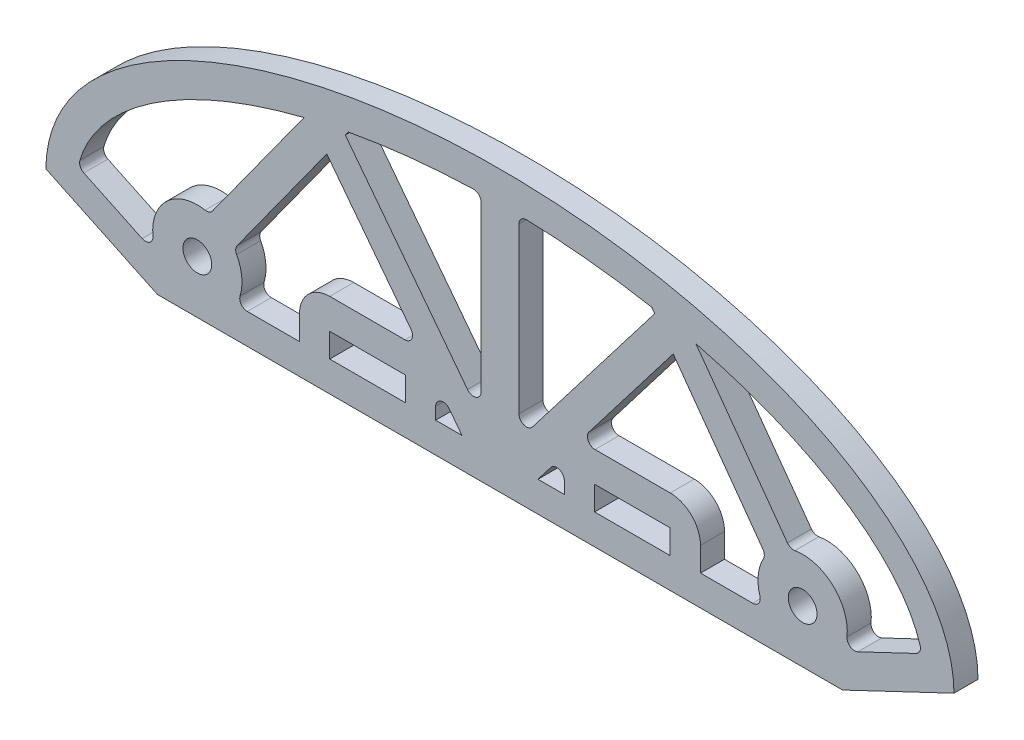
SolidWorks part; units mm, degrees
material "Mahogany"
ref_plane "Front Plane" through (0, 0, 0) normal (0, 0, 1) x (1, 0, 0)
ref_plane "Top Plane" through (0, 0, 0) normal (0, 1, 0) x (1, 0, 0)
ref_plane "Right Plane" through (0, 0, 0) normal (1, 0, 0) x (0, 0, -1)
sketch "Sketch3" plane through (0, 0, 0) normal (0, 0, 1) x (1, 0, 0)
  line L0 (85.2659, 27.2) -> (74.7341, 27.2) construction
  line L1 (74.7341, 27.2) -> (74.7341, 15.2) construction
  line L2 (74.7341, 15.2) -> (85.2659, 15.2) construction
  line L3 (85.2659, 15.2) -> (85.2659, 27.2) construction
  line L4 (5.2659, 27.2) -> (-5.2659, 27.2) construction
  line L5 (-5.2659, 27.2) -> (-5.2659, 15.2) construction
  line L6 (-5.2659, 15.2) -> (5.2659, 15.2) construction
  line L7 (5.2659, 15.2) -> (5.2659, 27.2) construction
  line L8 (85.2659, 27.2) -> (74.7341, 27.2) construction
  line L9 (74.7341, 27.2) -> (74.7341, 15.2) construction
  line L10 (74.7341, 15.2) -> (85.2659, 15.2) construction
  line L11 (85.2659, 15.2) -> (85.2659, 27.2) construction
  line L12 (5.2659, 27.2) -> (-5.2659, 27.2) construction
  line L13 (-5.2659, 27.2) -> (-5.2659, 15.2) construction
  line L14 (-5.2659, 15.2) -> (5.2659, 15.2) construction
  line L15 (5.2659, 15.2) -> (5.2659, 27.2) construction
  line L16 (0, 22.2) -> (80, 22.2) construction
  line L17 (-20, 22.2) -> (0, 22.2) construction
  line L18 (80, 22.2) -> (100, 22.2) construction
  line L19 (-20, 22.2) -> (-20, 52.2) construction
  line L20 (-20, 52.2) -> (40, 52.2) construction
  line L21 (-20, 22.2) -> (-5.2659, 15.2)
  line L22 (-5.2659, 15.2) -> (85.2659, 15.2)
  line L23 (85.2659, 15.2) -> (100, 22.2)
  line L24 (40, 52.2) -> (40, 15.2) construction
  line L25 (52.5, 22.375) -> (52.5, 19.2)
  line L26 (17.5, 22.375) -> (27.5, 22.375)
  line L27 (17.5, 22.375) -> (17.5, 19.2)
  line L28 (17.5, 19.2) -> (27.5, 19.2)
  line L29 (27.5, 22.375) -> (27.5, 19.2)
  line L30 (62.5, 19.2) -> (52.5, 19.2)
  line L31 (62.5, 22.375) -> (62.5, 19.2)
  line L32 (62.5, 22.375) -> (52.5, 22.375)
  circle A0 centre (80, 22.2) radius 1.9 construction
  circle A1 centre (0, 22.2) radius 1.9 construction
  circle A2 centre (80, 22.2) radius 1.9
  circle A3 centre (0, 22.2) radius 1.9
  ellipse E0 centre (40, 22.2) end of major axis (100, 22.2) minor radius 30 (100, 22.2) -> (-20, 22.2) ccw
  dimension "D1" = 30
  dimension "D2" = 60
  dimension "D3" = 10
  dimension "D4" = 3.175
  dimension "D5" = 4
  dimension "D6" = 25
extrude "Boss-Extrude1" add sketch "Sketch3" along normal blind 3.175
sketch "Sketch4" plane through (0, 0, 3.175) normal (0, 0, 1) x (1, 0, 0)
  line L0 (-15.7375, 24.6034) -> (-5.3232, 19.6557)
  line L1 (5.0804, 19.2) -> (74.9196, 19.2)
  line L2 (85.3232, 19.6557) -> (95.7375, 24.6034)
  line L3 (85.2659, 15.2) -> (100, 22.2)
  line L4 (52.5, 22.375) -> (52.5, 19.2)
  line L5 (62.5, 22.375) -> (52.5, 22.375)
  line L6 (62.5, 19.2) -> (62.5, 22.375)
  line L7 (52.5, 19.2) -> (62.5, 19.2)
  line L8 (52.5, 22.375) -> (52.5, 19.2) construction
  line L9 (62.5, 22.375) -> (52.5, 22.375) construction
  line L10 (62.5, 19.2) -> (62.5, 22.375) construction
  line L11 (52.5, 19.2) -> (62.5, 19.2) construction
  line L12 (17.5, 19.2) -> (27.5, 19.2)
  line L13 (17.5, 22.375) -> (17.5, 19.2)
  line L14 (27.5, 22.375) -> (17.5, 22.375)
  line L15 (27.5, 19.2) -> (27.5, 22.375)
  line L16 (17.5, 19.2) -> (27.5, 19.2) construction
  line L17 (17.5, 22.375) -> (17.5, 19.2) construction
  line L18 (27.5, 22.375) -> (17.5, 22.375) construction
  line L19 (27.5, 19.2) -> (27.5, 22.375) construction
  line L20 (-20, 22.2) -> (-5.2659, 15.2)
  line L21 (-5.2659, 15.2) -> (85.2659, 15.2)
  line L22 (85.2659, 15.2) -> (100, 22.2) construction
  line L23 (-20, 22.2) -> (-5.2659, 15.2) construction
  line L24 (-5.2659, 15.2) -> (85.2659, 15.2) construction
  line L25 (17.5, 26.375) -> (27.5, 26.375)
  line L26 (13.5, 22.375) -> (13.5, 19.2)
  line L27 (31.5, 22.375) -> (31.5, 19.2)
  line L28 (40, 15.2) -> (40, 52.2) construction
  line L29 (48.5, 22.375) -> (48.5, 19.2)
  line L30 (62.5, 26.375) -> (52.5, 26.375)
  line L31 (66.5, 22.375) -> (66.5, 19.2)
  line L32 (-4.364, 19.2) -> (84.364, 19.2) construction
  line L33 (-15.7375, 24.6034) -> (-4.364, 19.2) construction
  line L34 (84.364, 19.2) -> (95.7375, 24.6034) construction
  line L35 (37.5, 48.2) -> (42.5, 48.2)
  line L36 (37.5, 48.2) -> (37.5, 19.2)
  line L37 (37.5, 19.2) -> (42.5, 19.2)
  line L38 (42.5, 48.2) -> (42.5, 19.2)
  line L39 (17.0606, 45.8325) -> (37.5, 19.2) construction
  line L40 (14.9152, 45.3431) -> (34.9789, 19.2)
  line L41 (37.5, 22.485) -> (19.2406, 46.277)
  line L42 (24.947, 32.2715) -> (28.1202, 34.7068) construction
  line L43 (0, 22.2) -> (17.0606, 45.8325) construction
  line L44 (14.0952, 45.1417) -> (1.6274, 27.8711)
  line L45 (4.8705, 25.5298) -> (19.5537, 45.8691)
  line L46 (7.8613, 36.5064) -> (11.1045, 34.1651) construction
  line L47 (42.5, 19.2) -> (62.9394, 45.8325) construction
  line L48 (62.9394, 45.8325) -> (80, 22.2) construction
  line L49 (60.7594, 46.277) -> (42.5, 22.485)
  line L50 (45.0211, 19.2) -> (65.0848, 45.3431)
  line L51 (75.1295, 25.5298) -> (60.0562, 46.4094)
  line L52 (78.3726, 27.8711) -> (65.9048, 45.1417)
  line L53 (51.6297, 34.381) -> (54.8029, 31.9457) construction
  line L54 (72.1387, 36.5064) -> (68.8955, 34.1651) construction
  line L55 (19.5537, 45.8691) -> (19.9438, 46.4094)
  arc A0 (85.3232, 19.6557) -> (74.9196, 19.2) centre (80, 22.2) ccw
  circle A1 centre (80, 22.2) radius 1.9
  circle A2 centre (80, 22.2) radius 1.9 construction
  circle A3 centre (0, 22.2) radius 1.9
  circle A4 centre (0, 22.2) radius 1.9 construction
  arc A5 (5.0804, 19.2) -> (-5.3232, 19.6557) centre (0, 22.2) ccw
  circle A7 centre (0, 22.2) radius 5.9 construction
  circle A8 centre (80, 22.2) radius 5.9 construction
  arc A10 (17.5, 26.375) -> (13.5, 22.375) centre (17.5, 22.375) ccw
  arc A11 (31.5, 22.375) -> (27.5, 26.375) centre (27.5, 22.375) ccw
  arc A12 (48.5, 22.375) -> (52.5, 26.375) centre (52.5, 22.375) cw
  arc A13 (62.5, 26.375) -> (66.5, 22.375) centre (62.5, 22.375) cw
  arc A14 (28.2377, 27.9838) -> (27.4444, 26.375) centre (27.4444, 27.375) cw
  arc A15 (33.2933, 21.3963) -> (31.5, 20.7875) centre (32.5, 20.7875) ccw
  arc A16 (48.5, 20.7875) -> (46.7067, 21.3963) centre (47.5, 20.7875) ccw
  arc A17 (52.5556, 26.375) -> (51.7623, 27.9838) centre (52.5556, 27.375) cw
  ellipse E1 centre (40, 22.2) end of major axis (100, 22.2) minor radius 30 (100, 22.2) -> (-20, 22.2) ccw
  ellipse E2 centre (40, 22.2) end of major axis (100, 22.2) minor radius 30 (100, 22.2) -> (-20, 22.2) ccw construction
  spline S0 degree 1 poles (95.7375, 24.6034) (-15.7375, 24.6034) knots 0 0 1 1 construction
  spline S1 degree 3 poles (95.7375, 24.6034) (95.6622, 24.948) (95.4837, 25.6219) (94.9892, 27.0049) (94.1127, 28.758) (92.6161, 30.899) (90.0114, 33.7557) (85.6121, 37.2373) (78.6564, 40.9913) (71.8583, 43.5232) (67.3393, 44.7824) (65.7688, 45.1759) (65.4958, 45.2432) (65.2221, 45.3101) (64.7849, 45.4153) (64.1815, 45.5566) (63.356, 45.7431) (62.5185, 45.9239) (61.6693, 46.0987) (61.0635, 46.2186) (60.6425, 46.2994) (60.4083, 46.3438) (60.1738, 46.3877) (57.6339, 46.8566) (52.6559, 47.584) (44.2604, 48.2378) (35.7396, 48.2378) (27.3441, 47.584) (22.3661, 46.8566) (19.8262, 46.3877) (19.5917, 46.3438) (19.3575, 46.2994) (18.9365, 46.2186) (18.3307, 46.0987) (17.4815, 45.9239) (16.644, 45.7431) (15.8185, 45.5566) (15.2151, 45.4153) (14.7779, 45.3101) (14.5042, 45.2432) (14.2312, 45.1759) (12.6607, 44.7824) (8.1417, 43.5232) (1.3436, 40.9913) (-5.6121, 37.2373) (-10.0114, 33.7557) (-12.6161, 30.899) (-14.1127, 28.758) (-14.9892, 27.0049) (-15.4837, 25.6219) (-15.6622, 24.948) (-15.7375, 24.6034) knots 3.250373 3.250373 3.250373 3.250373 3.296061 3.341749 3.433125 3.524501 3.615877 3.798629 3.981381 4.164133 4.243947 4.251896 4.25587 4.259844 4.267792 4.281193 4.294593 4.31502 4.328713 4.342405 4.348917 4.352174 4.35543 4.361942 4.492953 4.623963 4.800815 4.931825 5.062836 5.069348 5.072604 5.075861 5.082373 5.096065 5.109758 5.130185 5.143585 5.156986 5.164934 5.168908 5.172882 5.180831 5.260645 5.443397 5.626149 5.808901 5.900277 5.991653 6.083029 6.128717 6.174405 6.174405 6.174405 6.174405
  point P42 (85.9, 22.2)
  point P43 (5.9, 22.2)
  point P53 (40, 19.2)
  point P54 (40, 48.2)
  point P68 (26.5336, 33.4892)
  point P75 (9.4829, 35.3358)
  point P79 (53.2163, 33.1633)
  point P82 (70.5171, 35.3358)
  point P104 (0, 0)
  point P105 (0, 0)
  point P106 (47.0571, 21.8529)
  dimension "D7" = 4
  dimension "D10" = 4
  dimension "D14" = 1
  dimension "D9" = 5
  dimension "D11" = 4
  dimension "D12" = 4
  dimension "D13" = 4
  dimension "D1" = 0
  dimension "D2" = 0
  dimension "D3" = 0
  dimension "D4" = 0
  dimension "D5" = 0
  dimension "D6" = 4
  dimension "D8" = 4
extrude "Cut-Extrude2" cut sketch "Sketch4" against normal up to surface (3.175 mm away) contours L44 S1 L0 A5 | A14 L40 L45 A5 L1 L26 A10 L25 | L36 S1 L55 L41 | L40 A15 L27 L1 | L51 S1 L38 L49 | L29 A16 L50 L1 | A17 L30 A13 L31 L1 A0 L51 L50 | L2 S1 L52 A0 region at (-2.3557, 32.6493, 3.175) region at (15.5054, 29.6634, 3.175) region at (31.3607, 39.1382, 3.175) region at (32.846, 20.2705, 3.175) region at (48.6393, 39.1382, 3.175) region at (47.154, 20.2705, 3.175) region at (64.4946, 29.6634, 3.175) region at (82.3557, 32.6493, 3.175) up to face at (57.5, 20.7875, 0)
fillet "Fillet1" radius 1 14 edges at (95.7375, 24.6034, 1.5875) (-15.7375, 24.6034, 1.5875) (-5.3232, 19.6557, 1.5875) (5.0804, 19.2, 1.5875) (4.8705, 25.5298, 1.5875) (1.6274, 27.8711, 1.5875) (37.5, 22.485, 1.5875) (37.5, 48.173, 1.5875) (42.5, 48.173, 1.5875) (42.5, 22.485, 1.5875) (85.3232, 19.6557, 1.5875) (78.3726, 27.8711, 1.5875) (74.9196, 19.2, 1.5875) (75.1295, 25.5298, 1.5875)
equation "\"prop-dist\"= 80mm"
equation "\"prop-hole-depth\"= 9mm"
equation "\"prop-hole-diameter\"= 11mm"
equation "\"rivet-extension\"= 12mm"
equation "\"rivet-hole-extension\"= 7mm"
equation "\"rivet-hole-diameter\"= 3.8mm"
equation "\"ski-length\"= 100mm"
equation "\"th\"= 0.125in'material thickness"
equation "\"ski-height\"= 30mm"
equation "\"ski-curve-gap\"= 60mm"
equation "\"ski-curve-height\"= \"rivet-hole-extension\""
equation "\"min-width\"= 4mm"
equation "\"prop-hole-diameter-small\"= 8.6mm"
equation "\"prop-dist-width\"= 86.5mm"
equation "\"prop-dist-length\"= 80mm"
equation "\"prop-boost\"= 4.4mm"
equation "\"back-drop\"= 5mm"
equation "\"T\"= 0.125in'Material Thickness"
equation "\"tof_c2c\"= 19.9mm'Center to center distance of TOF sensor holes"
equation "\"tof_d\"= 3mm'TOF hole diameter"
equation "\"tof_w\"= 12.6mm'TOF width"
equation "\"tof_l\"= 15.6mm'TOF length"
equation "\"pin_w\"= 2.3mm'A standard IO Pin socket width"
equation "\"pin_l\"= 2.5mm'A standard IO Pin socket length"
equation "\"esp_pin_num\"= 8'Number of pins on one side of the ESP"
equation "\"esp_l\"= 40mm'ESP length"
equation "\"esp_w\"= 27mm'ESP width"
equation "\"esp_pin_inset\"= 3mm'Distance that ESP pins are inset"
equation "\"bat_l\"= 27mm'Battery length"
equation "\"bat_w\"= 20mm'Battery width"
equation "\"bat_h\"= 6mm'Battery thickness"
equation "\"boost_w\"= 17.2mm"
equation "\"boost_l\"= 37mm"
equation "\"boost_hole_inset\"= 2.2mm"
equation "\"boost_hole_dist\"= 7mm"
equation "\"boost_hole_d\"= 2mm"
equation "\"support_width\"= 10mm"
equation "\"support_gap\"= 25mm"
equation "\"D1@Sketch3\"=\"ski-height\""
equation "\"D2@Sketch3\"=\"ski-curve-gap\""
equation "\"D3@Sketch3\"=\"support_width\""
equation "\"D4@Sketch3\"=\"T\""
equation "\"D6@Sketch3\"=\"support_gap\""
equation "\"D1@Boss-Extrude1\"=\"T\""
